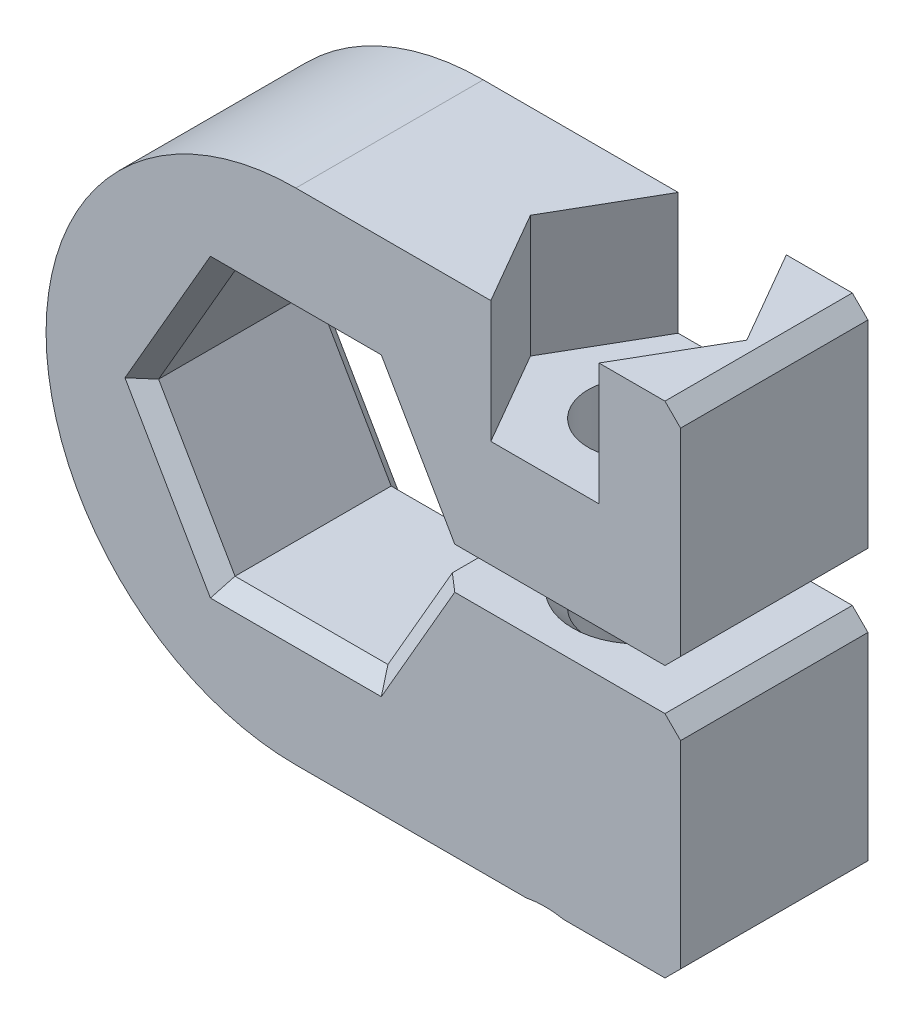
SolidWorks part; units mm, degrees
material "PET"
ref_plane "Front Plane" through (0, 0, 0) normal (0, 0, 1) x (1, 0, 0)
ref_plane "Top Plane" through (0, 0, 0) normal (0, 1, 0) x (1, 0, 0)
ref_plane "Right Plane" through (0, 0, 0) normal (1, 0, 0) x (0, 0, -1)
sketch "Sketch2" plane through (0, 0, 0) normal (0, 0, 1) x (1, 0, 0)
  line L0 (9.779, -12.7) -> (9.779, -1.0583) construction
  line L1 (3.8861, 6.731) -> (-3.8861, 6.731) construction
  line L2 (-3.8861, 6.731) -> (-7.7723, 0) construction
  line L3 (-7.7723, 0) -> (-3.8861, -6.731) construction
  line L4 (-3.8861, -6.731) -> (3.8861, -6.731) construction
  line L5 (3.8861, -6.731) -> (7.7723, 0) construction
  line L6 (7.7723, 0) -> (3.8861, 6.731) construction
  line L8 (3.8861, -6.731) -> (7.1613, -1.0583)
  line L9 (-3.8861, -6.731) -> (3.8861, -6.731)
  line L10 (-7.7723, 0) -> (-3.8861, -6.731)
  line L11 (-3.8861, 6.731) -> (-7.7723, 0)
  line L12 (3.8861, 6.731) -> (-3.8861, 6.731)
  line L13 (7.1613, 1.0583) -> (3.8861, 6.731)
  line L14 (9.779, 1.0583) -> (7.1613, 1.0583)
  line L15 (7.1613, -1.0583) -> (9.779, -1.0583)
  line L32 (9.779, 1.0583) -> (19.558, 1.0583)
  line L34 (19.558, 1.0583) -> (19.558, 12.7)
  line L36 (19.558, 12.7) -> (0, 12.7)
  line L37 (0, -12.7) -> (19.558, -12.7)
  line L39 (19.558, -12.7) -> (19.558, -1.0583)
  line L41 (19.558, -1.0583) -> (9.779, -1.0583)
  line L48 (15.875, 1.0583) -> (8.9943, 1.0583) construction
  line L49 (0, 12.7) -> (15.875, 12.7) construction
  circle A0 centre (0, 0) radius 6.731 construction
  arc A2 (0, 12.7) -> (0, -12.7) centre (0, 0) ccw
  point P46 (-12.7, 0)
  dimension "D2" = 32.258
  dimension "D1" = 13.462
extrude "Boss-Extrude1" add sketch "Sketch2" along normal blind 9.525
chamfer "Chamfer1" distance 0.7937 angle 45 16 edges at (5.5237, -3.8947, 0) (0, -6.731, 0) (-5.8292, -3.3655, 0) (-5.8292, 3.3655, 0) (0, 6.731, 0) (5.5237, 3.8947, 0) (5.5237, 3.8947, 9.525) (0, 6.731, 9.525) (-5.8292, 3.3655, 9.525) (-5.8292, -3.3655, 9.525) (0, -6.731, 9.525) (5.5237, -3.8947, 9.525) (19.558, -12.7, 4.7625) (19.558, 12.7, 4.7625) (19.558, 1.0583, 4.7625) (19.558, -1.0583, 4.7625)
sketch "Sketch3" plane through (0, 12.7, 0) normal (0, 1, 0) x (1, 0, 0)
  line L0 (7.1613, -8.7312) -> (7.1613, -0.7938) construction
  line L1 (15.4102, -9.525) -> (18.1598, -4.7625)
  line L2 (19.558, -9.525) -> (19.558, 0) construction
  line L5 (18.1598, -4.7625) -> (15.4102, 0)
  line L6 (15.4102, 0) -> (9.9109, 0)
  line L7 (9.9109, 0) -> (7.1613, -4.7625)
  line L8 (7.1613, -4.7625) -> (9.9109, -9.525)
  line L9 (9.9109, -9.525) -> (15.4102, -9.525)
  circle A0 centre (12.6605, -4.7625) radius 2.5527
  circle A1 centre (12.6605, -4.7625) radius 4.7625 construction
  point P7 (19.558, -4.7625)
  dimension "D1" = 5.1054
  dimension "D2" = 9.525
extrude "Cut-Extrude1" cut sketch "Sketch3" against normal through all contours A0 region at (12.6605, 12.7, 4.7625)
sketch "Sketch4" plane through (0, 12.7, 0) normal (0, 1, 0) x (1, 0, 0)
  line L1 (9.9109, -9.525) -> (15.4102, -9.525)
  line L2 (15.4102, -9.525) -> (18.1598, -4.7625)
  line L3 (18.1598, -4.7625) -> (15.4102, 0)
  line L4 (15.4102, 0) -> (9.9109, 0)
  line L5 (9.9109, 0) -> (7.1613, -4.7625)
  line L6 (7.1613, -4.7625) -> (9.9109, -9.525)
  circle A0 centre (12.6605, -4.7625) radius 4.7625 construction
  dimension "D1" = 9.525
extrude "Cut-Extrude2" cut sketch "Sketch4" against normal blind 6.2
sketch "Sketch5" plane through (0, -12.7, 0) normal (0, -1, 0) x (1, 0, 0)
  circle A0 centre (12.6605, 4.7625) radius 4.064
  dimension "D1" = 8.128
extrude "Cut-Extrude3" cut sketch "Sketch5" against normal blind 6.35
chamfer "Chaflán1" distance 0.7937 angle 45 3 edges at (16.7245, -12.7, 4.7625) (15.2132, -1.0583, 4.7625) (12.6605, 1.0583, 7.3152)
